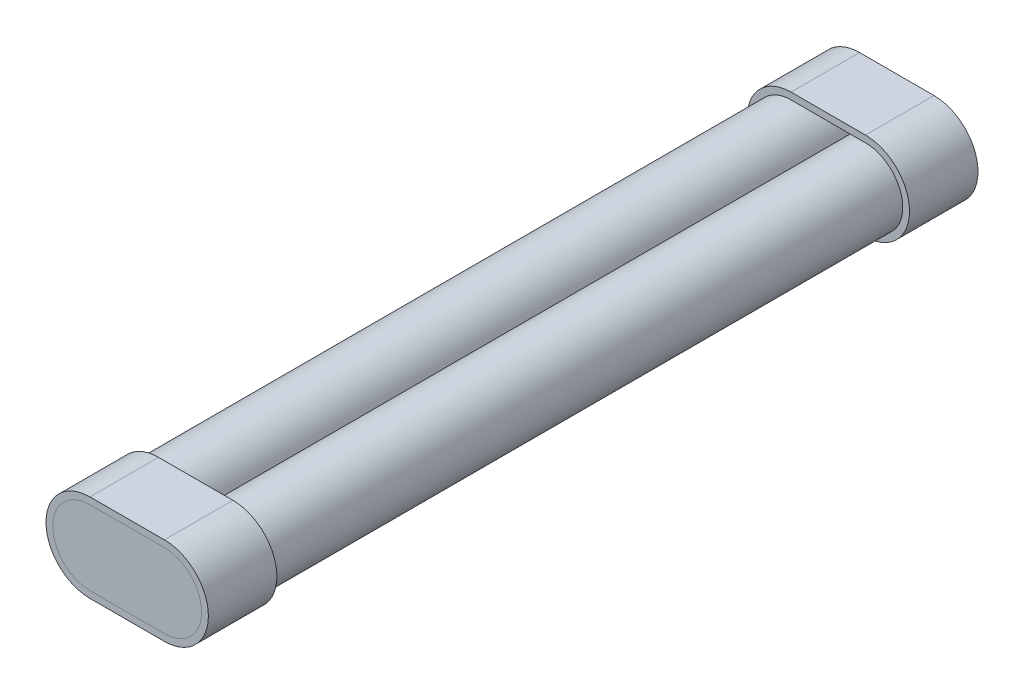
SolidWorks part; units mm, degrees
ref_plane "Plan de face" through (0, 0, 0) normal (0, 0, 1) x (1, 0, 0)
ref_plane "Plan de dessus" through (0, 0, 0) normal (0, 1, 0) x (1, 0, 0)
ref_plane "Plan de droite" through (0, 0, 0) normal (1, 0, 0) x (0, 0, -1)
sketch "Esquisse1" plane through (0, 0, 0) normal (0, 0, 1) x (1, 0, 0)
  line L0 (-11, -11) -> (11, -11)
  line L1 (-11, 0) -> (11, 0) construction
  line L2 (-11, 13) -> (11, 13)
  line L3 (-11, -13) -> (11, -13)
  line L4 (-11, 11) -> (11, 11)
  circle A0 centre (-11, 0) radius 11
  circle A1 centre (11, 0) radius 11
  arc A2 (-11, 13) -> (-11, -13) centre (-11, 0) ccw
  arc A3 (11, -13) -> (11, 13) centre (11, 0) ccw
  point P2 (0, 0)
  point P14 (-24, 0)
  point P15 (24, 0)
  dimension "D1" = 22
  dimension "D3" = 2
  dimension "D5" = 48
extrude "Boss.-Extru.2" add sketch "Esquisse1" against normal blind 223.5 contours A0 | A1 region at (-11, 0, 0) region at (11, 0, 0)
extrude "Boss.-Extru.8" add sketch "Esquisse1<5>" against normal blind 18.25 and the other way blind 2 separate body contours L3 A3 L2 A2 A1 L0 A0 L4 region at (0, 12.4541, 0)
sketch "Esquisse1<5>" plane through (0, 0, 0) normal (0, 0, 1) x (1, 0, 0) same geometry as "Esquisse1"
extrude "Boss.-Extru.29" add sketch "Esquisse1<6>" along normal blind 2 separate body contours A0 | A1 | A1 L4 A0 | A1 A0 L0 region at (0, -8.543, 0) region at (-11, 0, 0) region at (11, 0, 0) region at (0, 8.543, 0)
sketch "Esquisse1<6>" plane through (0, 0, 0) normal (0, 0, 1) x (1, 0, 0) same geometry as "Esquisse1"
sketch "Esquisse8" plane through (0, 0, -223.5) normal (0, 0, -1) x (-1, 0, 0)
  line L0 (-11, -11) -> (11, -11)
  line L1 (-11, 0) -> (11, 0) construction
  line L2 (-11, 13) -> (11, 13)
  line L3 (-11, -13) -> (11, -13)
  line L4 (-11, 11) -> (11, 11)
  circle A0 centre (-11, 0) radius 11
  circle A1 centre (11, 0) radius 11
  arc A2 (-11, 13) -> (-11, -13) centre (-11, 0) ccw
  arc A3 (11, -13) -> (11, 13) centre (11, 0) ccw
  point P2 (0, 0)
  point P13 (-24, 0)
  point P18 (24, 0)
  circle M8 centre (11, 0) radius 11
  dimension "D1" = 22
  dimension "D2" = 13
  dimension "D4" = 48
extrude "Boss.-Extru.33" add sketch "Esquisse8" against normal blind 18.25 and the other way blind 2 separate body contours L3 A3 L2 A2 A0 L4 L0 M8 region at (0, 12.4541, -223.5)
extrude "Boss.-Extru.34" add sketch "Esquisse8<3>" along normal blind 2 separate body contours A0 | A0 L4 M8 | M8 | A0 L0 M8 region at (0, -8.543, -223.5) region at (11, 0, -223.5) region at (-11, 0, -223.5) region at (0, 8.543, -223.5)
sketch "Esquisse8<3>" plane through (0, 0, -223.5) normal (0, 0, -1) x (-1, 0, 0) same geometry as "Esquisse8"
